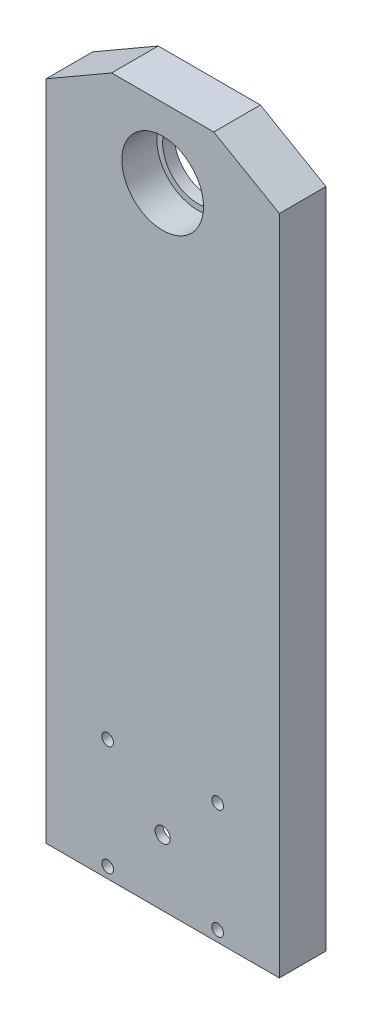
SolidWorks part; units mm, degrees
material "3.1325 (EN-AW 2017A)"
ref_plane "Płaszczyzna przednia" through (0, 0, 0) normal (0, 0, 1) x (1, 0, 0)
ref_plane "Płaszczyzna górna" through (0, 0, 0) normal (0, 1, 0) x (1, 0, 0)
ref_plane "Płaszczyzna prawa" through (0, 0, 0) normal (1, 0, 0) x (0, 0, -1)
other "Środek masy(COM)"
sketch "Szkic1" plane through (0, 0, 0) normal (0, 0, 1) x (1, 0, 0)
  line L0 (0, 0) -> (0, 300) construction
  line L1 (50, 0) -> (-50, 0)
  line L2 (-50, 0) -> (-50, 283.7766)
  line L3 (-21.9003, 300) -> (21.9003, 300)
  line L4 (-21.9003, 300) -> (-50, 283.7766)
  line L5 (21.9003, 300) -> (50, 283.7766)
  line L6 (50, 0) -> (50, 283.7766)
  line L7 (21.9003, 270) -> (-21.9003, 270) construction
  circle A0 centre (0, 270) radius 15
  circle A1 centre (0, 270) radius 17.5
  dimension "D3" = 300
  dimension "D5" = 30
  dimension "D6" = 35
  dimension "D1" = 30
  dimension "D2" = 50
  dimension "D4" = 30
extrude "Dodanie-wyciągnięcie1" add sketch "Szkic1" along normal blind 20 contours L1 L0 A1 L3 L4 L2 | L0 L1 L6 L5 L3 A1 region at (-25.3422, 143.6544, 0) region at (25.3422, 143.6544, 0)
extrude "Dodanie-wyciągnięcie2" add sketch "Szkic1<3>" along normal blind 5 contours A1 L0 A0 | L0 A1 A0 region at (-17.1087, 270, 0) region at (0.3913, 253.75, 0)
sketch "Szkic1<3>" plane through (0, 0, 0) normal (0, 0, 1) x (1, 0, 0) same geometry as "Szkic1"
sketch "Szkic2" plane through (0, 0, 0) normal (0, -1, 0) x (-1, 0, 0)
  line L0 (0, 0) -> (0, -20) construction
  line L1 (-50, -20) -> (50, -20) construction
  line L2 (-50, -10) -> (50, -10) construction
  line L3 (-50, -20) -> (-50, 0) construction
  line L4 (50, -20) -> (50, 0) construction
  point P11 (35, -10)
  point P12 (-35, -10)
  dimension "D1" = 70
hole_wizard "Otwór gwintowany M81" positions "Szkic 3D1" profile "Szkic3" tap size "M8" standard "ISO"
sketch3d "Szkic 3D1"
  point P0 (-35, 0, 10)
  point P3 (35, 0, 10)
sketch "Szkic3" plane through (-35, 0, 10) normal (1, 0, 0) x (0, 0, -1)
  line L0 (0, 0) -> (0, 42.0429)
  line L1 (0, 42.0429) -> (3.4, 40)
  line L2 (3.4, 40) -> (3.4, 0)
  line L5 (3.4, 0) -> (0, 0)
  line L10 (0, 42.0429) -> (-3.4, 40) construction
  line L11 (0, -6.35) -> (0, 107.95) construction
  dimension "Średnica wiertła gwintu" = 6.8
  dimension "Głębokość otworu gwintowanego" = 40
  dimension "Kąt wiertła" = 118
cosmetic thread "Gwint otworu1" parameters "D1"=30, "D2"=8
cosmetic thread "Gwint otworu2" parameters "D1"=30, "D2"=8
sketch "Szkic4" plane through (0, 0, 0) normal (0, 0, -1) x (-1, 0, 0)
  line L0 (50, 0) -> (50, 283.7766) construction
  line L1 (-28.2, 0) -> (28.2, 0)
  line L2 (-50, 0) -> (50, 0) construction
  line L3 (-28.2, 0) -> (-28.2, 53.4)
  line L4 (-25.2, 56.4) -> (25.2, 56.4)
  line L5 (28.2, 0) -> (28.2, 53.4)
  line L7 (-50, 0) -> (50, 0) construction
  arc A2 (28.2, 53.4) -> (25.2, 56.4) centre (25.2, 53.4) ccw
  arc A3 (-25.2, 56.4) -> (-28.2, 53.4) centre (-25.2, 53.4) ccw
  circle A4 centre (0, 28.2) radius 19.05
  circle A5 centre (0, 28.2) radius 3.25
  point P9 (0, 56.4)
  point P12 (-28.2, 0)
  point P15 (28.2, 0)
  point P18 (28.2, 56.4)
  point P21 (-28.2, 56.4)
  line M1 (-50, 0) -> (50, 0)
  dimension "D1" = 28.2
  dimension "D2" = 56.4
  dimension "D3" = 38.1
  dimension "D4" = 6.5
  dimension "D5" = 56.4
  dimension "D6" = 3
  dimension "D7" = 78.2
extrude "Wytnij-wyciągnięcie2" cut sketch "Szkic4" against normal blind 15 contours L4 A3 L3 L5 A2 A4 M1 | A4 A5 region at (27.4024, 26.7, 0) region at (18.5112, 28.2, 0)
extrude "Wytnij-wyciągnięcie3" cut sketch "Szkic4<4>" against normal blind 16.6 contours A4 A5 region at (18.5112, 28.2, 0)
sketch "Szkic4<4>" plane through (0, 0, 0) normal (0, 0, -1) x (-1, 0, 0) same geometry as "Szkic4"
extrude "Wytnij-wyciągnięcie4" cut sketch "Szkic4<5>" against normal blind 49.6 contours A5 region at (0, 28.2, 0)
sketch "Szkic4<5>" plane through (0, 0, 0) normal (0, 0, -1) x (-1, 0, 0) same geometry as "Szkic4"
sketch "Szkic5" plane through (0, 0, 15) normal (0, 0, -1) x (-1, 0, 0)
  line L0 (0, 28.2) -> (0, 56.4) construction
  line L1 (-25.2, 56.4) -> (25.2, 56.4) construction
  line L2 (0, 28.2) -> (-28.2, 28.2) construction
  line L3 (-28.2, 0) -> (-28.2, 53.4) construction
  point P17 (-23.57, 51.77)
  point P18 (-23.57, 4.63)
  point P19 (23.57, 4.63)
  point P20 (23.57, 51.77)
  dimension "D1" = 47.14
  dimension "D2" = 47.14
sketch "Szkic6" plane through (0, 0, 0) normal (0, 0, -1) x (-1, 0, 0)
  line L0 (0, 255) -> (0, 56.4) construction
  line L4 (-45, 228.9281) -> (-45, 82.4719)
  line L5 (2.2326, 145.7142) -> (38.3428, 74.0554)
  line L6 (45, 228.9281) -> (45, 82.4719)
  line L7 (-45, 245) -> (45, 66.4) construction
  line L8 (45, 245) -> (1.3997, 158.4777) construction
  line L9 (-40.0085, 240.65) -> (-2.2326, 165.6858)
  line L10 (-40.2674, 230.0531) -> (-5.0672, 160.2001)
  line L11 (40.0085, 240.65) -> (2.2326, 165.6858)
  line L12 (40.2674, 230.0531) -> (5.0672, 160.2001)
  line L13 (-35.6638, 69.7054) -> (35.6638, 69.7054)
  line L14 (-2.2326, 145.7142) -> (-38.3428, 74.0554)
  line L15 (-5.0672, 151.1999) -> (-40.2674, 81.3469)
  line L16 (0, 155.7) -> (-45, 66.4) construction
  line L17 (5.0672, 151.1999) -> (40.2674, 81.3469)
  line L18 (-37.3294, 245) -> (37.3294, 245)
  line L20 (-40.2674, 155.7) -> (38.3428, 155.7) construction
  line L21 (50, 0) -> (50, 283.7766) construction
  line L22 (28.2, 0) -> (50, 0) construction
  arc A1 (-40.2674, 230.0531) -> (-45, 228.9281) centre (-42.5, 228.9281) ccw
  arc A2 (-45, 82.4719) -> (-40.2674, 81.3469) centre (-42.5, 82.4719) ccw
  arc A3 (45, 82.4719) -> (40.2674, 81.3469) centre (42.5, 82.4719) cw
  arc A4 (-38.3428, 74.0554) -> (-35.6638, 69.7054) centre (-35.6638, 72.7054) ccw
  arc A5 (35.6638, 69.7054) -> (38.3428, 74.0554) centre (35.6638, 72.7054) ccw
  arc A6 (-37.3294, 245) -> (-40.0085, 240.65) centre (-37.3294, 242) ccw
  arc A7 (37.3294, 245) -> (40.0085, 240.65) centre (37.3294, 242) cw
  arc A8 (2.2326, 145.7142) -> (-2.2326, 145.7142) centre (0, 144.5892) ccw
  arc A9 (45, 228.9281) -> (40.2674, 230.0531) centre (42.5, 228.9281) ccw
  arc A10 (-5.0672, 151.1999) -> (-5.0672, 160.2001) centre (-13.9974, 155.7) ccw
  arc A11 (2.2326, 165.6858) -> (-2.2326, 165.6858) centre (0, 166.8108) cw
  arc A12 (5.0672, 151.1999) -> (5.0672, 160.2001) centre (13.9974, 155.7) cw
  dimension "D1" = 2.5
  dimension "D2" = 3
  dimension "D5" = 5
  dimension "D6" = 2.2326
  dimension "D3" = 10
  dimension "D4" = 95
  dimension "D7" = 0.259
  dimension "D8" = 1.6656
  dimension "D9" = 21.6663
  dimension "D10" = 66.4
extrude "Wytnij-wyciągnięcie6" cut sketch "Szkic6" against normal blind 10
hole_wizard "Otwór gwintowany M61" positions "Szkic 3D2" profile "Szkic7" tap size "M6" standard "ISO" end condition through all
sketch3d "Szkic 3D2"
  point P0 (23.57, 51.77, 15)
  point P3 (-23.57, 51.77, 15)
  point P6 (-23.57, 4.63, 15)
  point P9 (23.57, 4.63, 15)
sketch "Szkic7" plane through (23.57, 51.77, 15) normal (1, 0, 0) x (0, 1, 0)
  line L0 (0, 0) -> (0, 5)
  line L1 (0, 5) -> (2.5, 5)
  line L2 (2.5, 5) -> (2.5, 0)
  line L5 (2.5, 0) -> (0, 0)
  line L11 (0, -6.35) -> (0, 107.95) construction
  dimension "Średnica otworu gwintowanego na wylot" = 5
  dimension "Głębokość otworu gwintowanego na wylot" = 5
cosmetic thread "Gwint otworu3" parameters "D2"=6
cosmetic thread "Gwint otworu4" parameters "D2"=6
cosmetic thread "Gwint otworu5" parameters "D2"=6
cosmetic thread "Gwint otworu6" parameters "D2"=6
